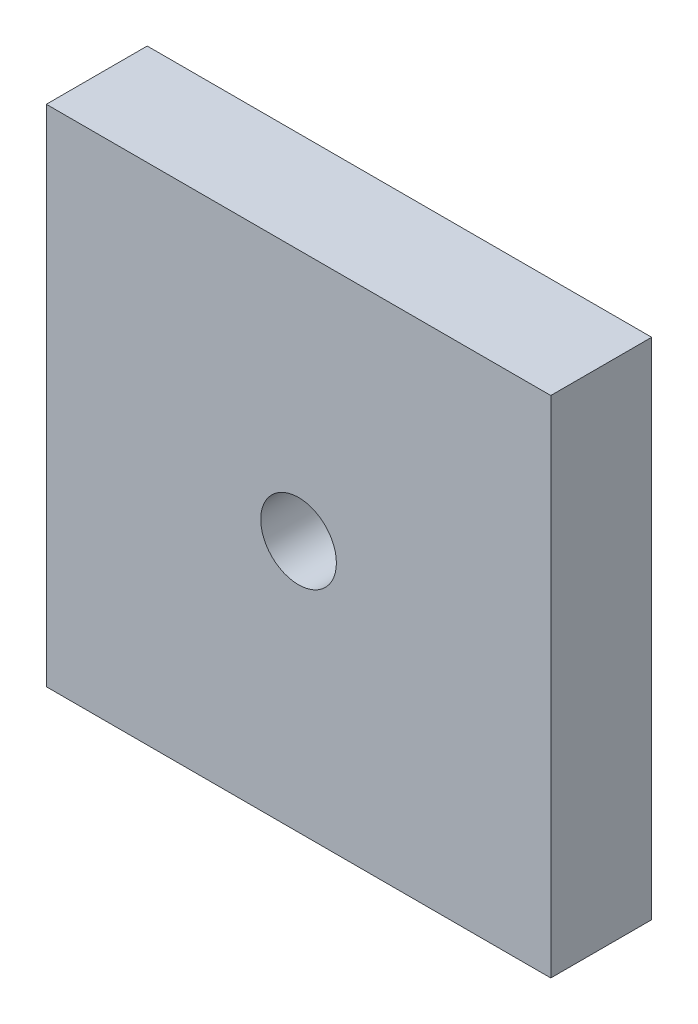
SolidWorks part; units mm, degrees
material "Cast Alloy Steel"
ref_plane "Front Plane" through (0, 0, 0) normal (0, 0, 1) x (1, 0, 0)
ref_plane "Top Plane" through (0, 0, 0) normal (0, 1, 0) x (1, 0, 0)
ref_plane "Right Plane" through (0, 0, 0) normal (1, 0, 0) x (0, 0, -1)
sketch "Sketch1" plane through (0, 0, 0) normal (0, 0, 1) x (1, 0, 0)
  line L1 (-10, -10) -> (10, -10)
  line L2 (-10, -10) -> (-10, 10)
  line L3 (-10, 10) -> (10, 10)
  line L4 (10, -10) -> (10, 10)
  line L5 (-10, -10) -> (10, 10) construction
  line L6 (-10, 10) -> (10, -10) construction
  circle A0 centre (0, 0) radius 1.5
  point P0 (0, 0)
  dimension "D3" = 3
  dimension "D1" = 20
  dimension "D2" = 20
extrude "Boss-Extrude1" add sketch "Sketch1" along normal blind 4
